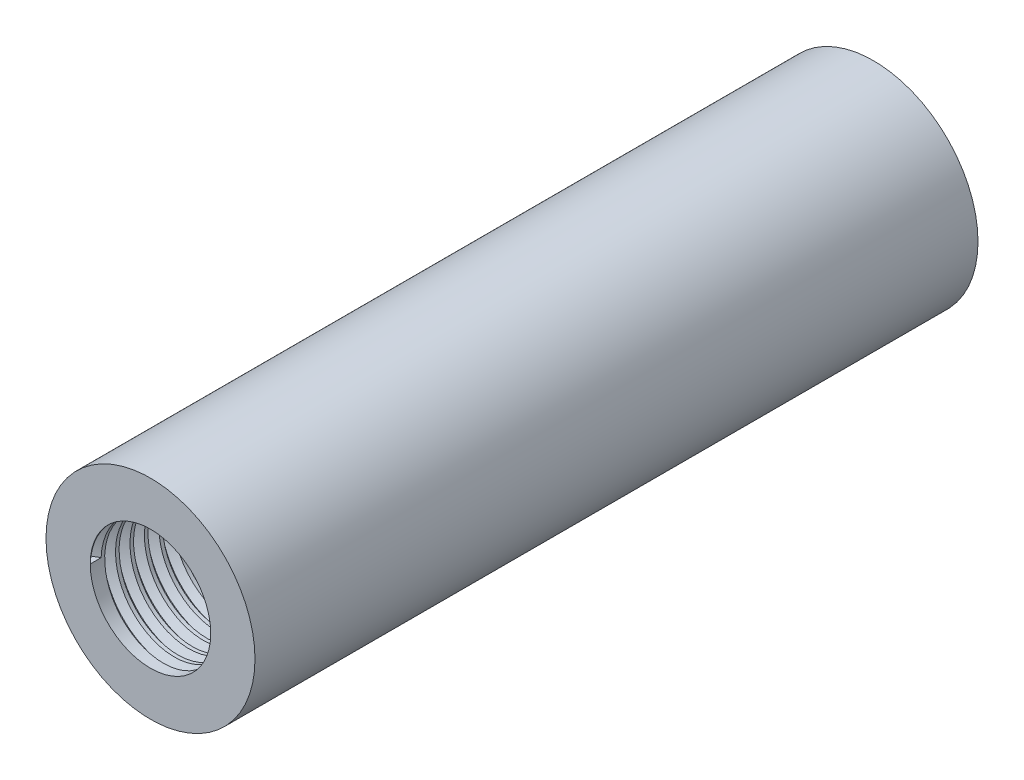
SolidWorks part; units mm, degrees
ref_plane "Front Plane" through (0, 0, 0) normal (0, 0, 1) x (1, 0, 0)
ref_plane "Top Plane" through (0, 0, 0) normal (0, 1, 0) x (1, 0, 0)
ref_plane "Right Plane" through (0, 0, 0) normal (1, 0, 0) x (0, 0, -1)
sketch "Sketch1" plane through (0, 0, 0) normal (0, 0, 1) x (1, 0, 0)
  circle A1 centre (0, 0) radius 10.84
  dimension "D1" = 21.68
extrude "Boss-Extrude1" add sketch "Sketch1" along normal blind 75
sketch "Sketch2" plane through (0, 0, 75) normal (0, 0, 1) x (1, 0, 0)
  circle A0 centre (0, 0) radius 6.25
  dimension "D1" = 12.5
extrude "Cut-Extrude1" cut sketch "Sketch2" against normal through all
thread "Thread1" pitch 1.5 method cut profile "Thread Profile1" start angle 0, offset 0, length 19, pitch 1.5, diameter 12.5
ref_plane "Plane1" through (-6.25, 0, 75) normal (0, -1, 0) x (-1, 0, 0)
sketch "Thread Profile1" plane through (-6.25, 0, 75) normal (0, -1, 0) x (-1, 0, 0)
  line L0 (0, 0) -> (0, 1.5) construction
  line L1 (0, 0) -> (0.8119, 0.4687)
  line L2 (0.8119, 0.4687) -> (0.8119, 0.6562)
  line L3 (0.8119, 0.6562) -> (0, 1.125)
  line L4 (0.8119, 0.5625) -> (0, 0.5625) construction
  line L11 (0, 0) -> (0, 1.125)
  point P2 (0, 0)
  dimension "Pitch" = 1.5
  dimension "Profile_Angle" = 60
  dimension "Profile_Land" = 0.1875
  dimension "Profile_Height" = 0.8119
thread "Thread2" pitch 1.5 method cut profile "Thread Profile2" start angle 0, offset 0, length 19, pitch 1.5, diameter 12.5
ref_plane "Plane2" through (6.25, 0, 0) normal (0, -1, 0) x (1, 0, 0)
sketch "Thread Profile2" plane through (6.25, 0, 0) normal (0, -1, 0) x (1, 0, 0)
  line L0 (0, 0) -> (0, 1.5) construction
  line L1 (0, 0) -> (0.8119, 0.4687)
  line L2 (0.8119, 0.4687) -> (0.8119, 0.6562)
  line L3 (0.8119, 0.6562) -> (0, 1.125)
  line L4 (0.8119, 0.5625) -> (0, 0.5625) construction
  line L11 (0, 0) -> (0, 1.125)
  point P2 (0, 0)
  dimension "Pitch" = 1.5
  dimension "Profile_Angle" = 60
  dimension "Profile_Land" = 0.1875
  dimension "Profile_Height" = 0.8119
sketch3d "3DSketch1"
  line L0 (0, 0, 0) -> (0, 0, 68.87) construction
  line L1 (0, 0, 0) -> (0, 0, 75) construction
  line L2 (0, 0, 75) -> (0, 0, 0) construction
